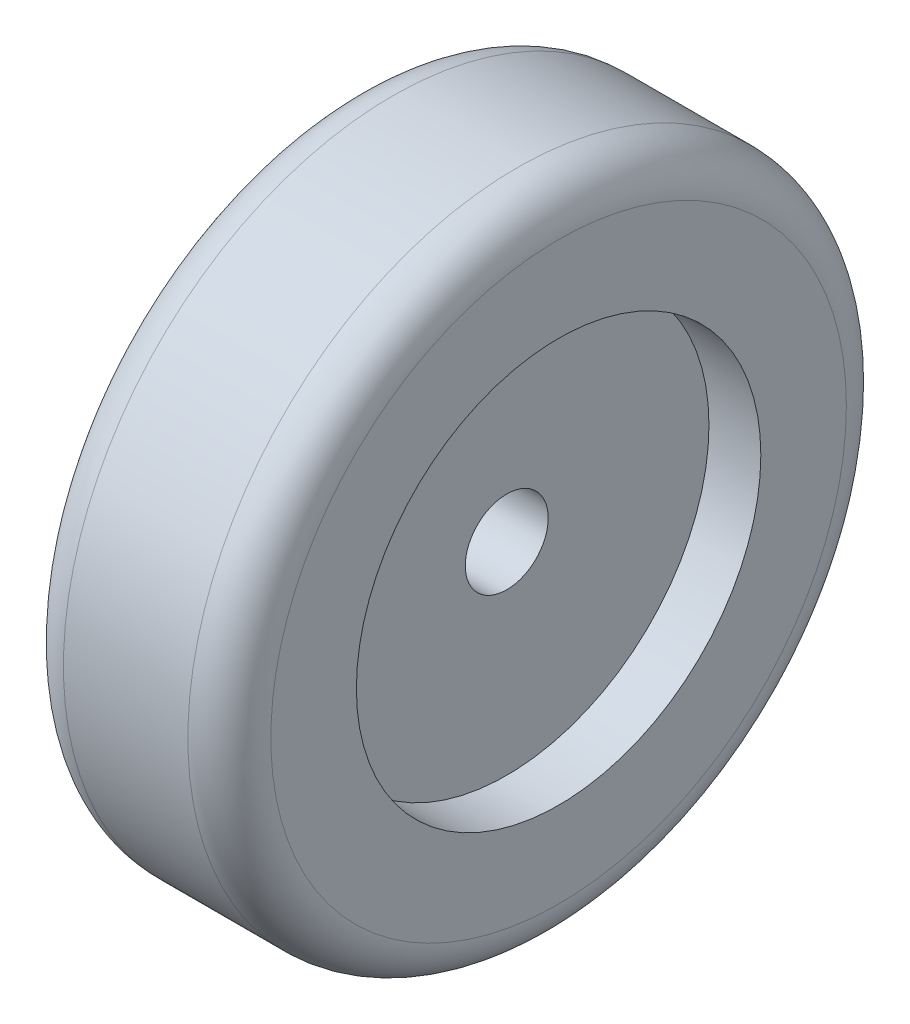
SolidWorks part; units mm, degrees
ref_plane "Alzado" through (0, 0, 0) normal (0, 0, 1) x (1, 0, 0)
ref_plane "Planta" through (0, 0, 0) normal (0, 1, 0) x (1, 0, 0)
ref_plane "Vista lateral" through (0, 0, 0) normal (1, 0, 0) x (0, 0, -1)
sketch "Croquis1" plane through (0, 0, 0) normal (0, 0, 1) x (1, 0, 0)
  line L0 (9, 4) -> (9, 19.5)
  line L1 (9, 19.5) -> (14, 19.5)
  line L2 (14, 19.5) -> (14, 27.75)
  line L3 (10, 31.75) -> (-2, 31.75)
  line L4 (-6, 27.75) -> (-6, 19.5)
  line L5 (-6, 19.5) -> (-9, 10)
  line L6 (-9, 10) -> (-9, 4)
  line L8 (-9, 4) -> (9, 4)
  line L10 (0, 0) -> (-24.0785, 0) construction
  arc A0 (14, 27.75) -> (10, 31.75) centre (10, 27.75) ccw
  arc A1 (-2, 31.75) -> (-6, 27.75) centre (-2, 27.75) ccw
  point P10 (0, 4)
  point P16 (14, 31.75)
  point P19 (-6, 31.75)
  dimension "D7" = 4
  dimension "D1" = 4
  dimension "D2" = 23
  dimension "D3" = 19.5
  dimension "D4" = 5
  dimension "D5" = 20
  dimension "D6" = 31.75
  dimension "D8" = 10
revolve "Revolución1" add sketch "Croquis1" angle 360 about L10
